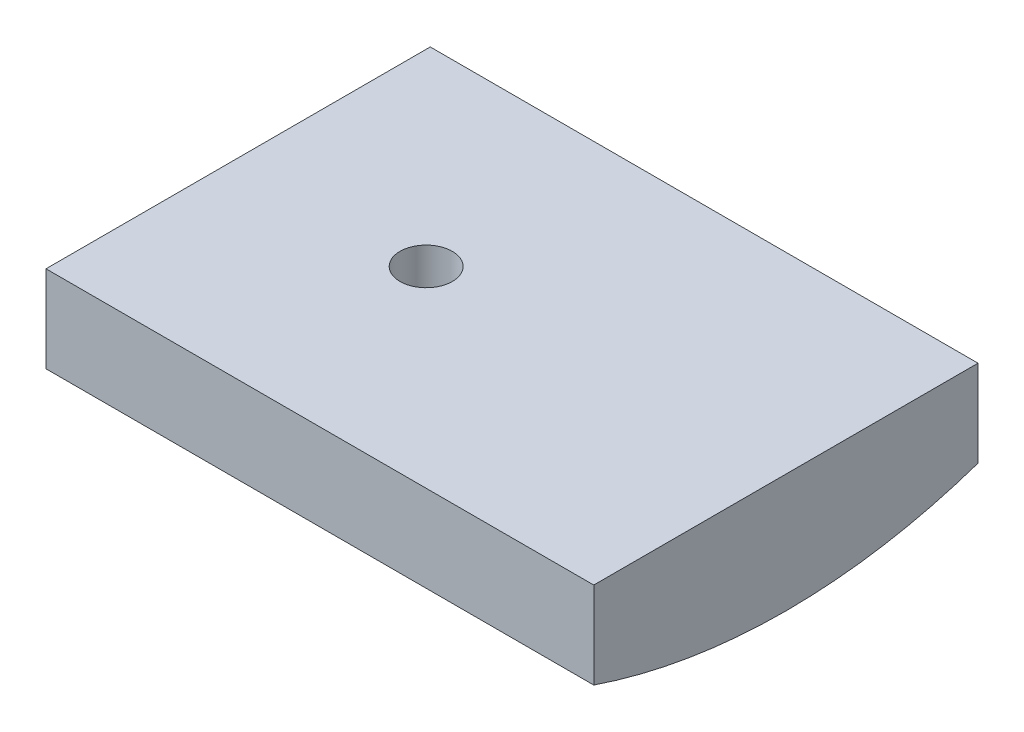
SolidWorks part; units mm, degrees
ref_plane "Front Plane" through (0, 0, 0) normal (0, 0, 1) x (1, 0, 0)
ref_plane "Top Plane" through (0, 0, 0) normal (0, 1, 0) x (1, 0, 0)
ref_plane "Right Plane" through (0, 0, 0) normal (1, 0, 0) x (0, 0, -1)
sketch "Sketch1" plane through (0, 0, 0) normal (1, 0, 0) x (0, 0, -1)
  line L0 (0, 0) -> (0, -90.5205) construction
  line L1 (-23.5, -58.2) -> (23.5, -58.2)
  line L2 (-23.5, -58.2) -> (-23.5, -68.7971)
  line L4 (23.5, -58.2) -> (23.5, -68.7971)
  arc A0 (-23.5, -68.7971) -> (23.5, -68.7971) centre (0, 0) ccw construction
  arc A1 (-23.5, -68.7971) -> (23.5, -68.7971) centre (0, 0) ccw
  circle A2 centre (0, 0) radius 72.7 construction
  point P7 (0, -72.7)
  dimension "D1" = 145.4
  dimension "D2" = 14.5
  dimension "D3" = 47
extrude "Boss-Extrude1" add sketch "Sketch1" along normal blind 67
sketch "Sketch2" plane through (0, -58.2, 0) normal (0, 1, 0) x (1, 0, 0)
  line L0 (0, 23.5) -> (67, -23.5) construction
  line L1 (0, -23.5) -> (67, 23.5) construction
  line L2 (23, 0) -> (33.5, 0) construction
  line L4 (67, 23.5) -> (67, -23.5) construction
  circle A0 centre (23, 0) radius 3.2
  point P10 (26.1359, 0)
  point P13 (33.5, 0)
  point P14 (19.7399, 0)
  dimension "D1" = 6.4
  dimension "D2" = 44
extrude "Cut-Extrude1" cut sketch "Sketch2" against normal through all
